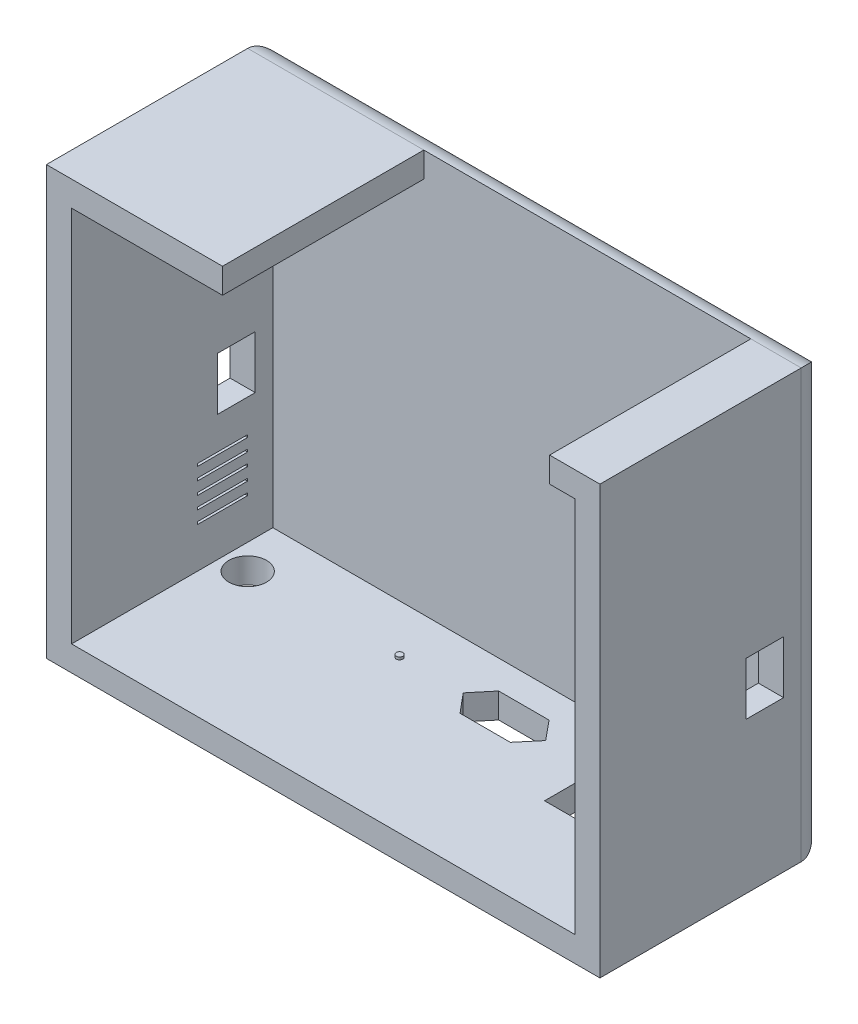
SolidWorks part; units mm, degrees
ref_plane "Front Plane" through (0, 0, 0) normal (0, 0, 1) x (1, 0, 0)
ref_plane "Top Plane" through (0, 0, 0) normal (0, 1, 0) x (1, 0, 0)
ref_plane "Right Plane" through (0, 0, 0) normal (1, 0, 0) x (0, 0, -1)
sketch "Sketch1" plane through (0, 0, 0) normal (0, 0, 1) x (1, 0, 0)
  line L1 (-465.1793, 299.9736) -> (-245.1793, 299.9736)
  line L2 (-465.1793, 299.9736) -> (-465.1793, 129.9736)
  line L3 (-465.1793, 129.9736) -> (-245.1793, 129.9736)
  line L4 (-245.1793, 299.9736) -> (-245.1793, 129.9736)
  dimension "D1" = 170
  dimension "D2" = 220
extrude "Boss-Extrude1" add sketch "Sketch1" along normal blind 100
sketch "Sketch3" plane through (0, 0, 100) normal (0, 0, 1) x (1, 0, 0)
  line L1 (-455.1793, 289.9736) -> (-255.1793, 289.9736)
  line L2 (-455.1793, 289.9736) -> (-455.1793, 139.9736)
  line L3 (-455.1793, 139.9736) -> (-255.1793, 139.9736)
  line L4 (-255.1793, 289.9736) -> (-255.1793, 139.9736)
  dimension "D1" = 10
  dimension "D2" = 10
  dimension "D3" = 10
  dimension "D4" = 10
  dimension "D5" = 10
  dimension "D6" = 150
  dimension "D7" = 200
extrude "Cut-Extrude2" cut sketch "Sketch3" against normal blind 90
fillet "Fillet1" radius 10 4 edges at (-355.1793, 129.9736, 0) (-245.1793, 214.9736, 0) (-355.1793, 299.9736, 0) (-465.1793, 214.9736, 0)
sketch "Sketch4" plane through (0, 299.9736, 0) normal (0, 1, 0) x (1, 0, 0)
  line L0 (-245.1793, -10) -> (-465.1793, -10) construction
  line L1 (-265.1793, -100) -> (-395.1793, -100)
  line L2 (-265.1793, -100) -> (-265.1793, -10)
  line L3 (-265.1793, -10) -> (-395.1793, -10)
  line L4 (-395.1793, -100) -> (-395.1793, -10)
  line L5 (-255.1793, -10) -> (-255.1793, -100) construction
  line L7 (-245.1793, -100) -> (-465.1793, -100) construction
  dimension "D1" = 10
  dimension "D2" = 0
  dimension "D3" = 130
  dimension "D4" = 90
extrude "Cut-Extrude3" cut sketch "Sketch4" against normal blind 10
ref_plane "Plane1" through (0, 0, 90) normal (0, 0, 1) x (1, 0, 0)
sketch "Sketch8" plane through (0, 0, 90) normal (0, 0, 1) x (1, 0, 0)
  line L1 (-466.5662, 301.0824) -> (-243.038, 301.0824)
  line L2 (-466.5662, 301.0824) -> (-466.5662, 129.2049)
  line L3 (-466.5662, 129.2049) -> (-243.038, 129.2049)
  line L4 (-243.038, 301.0824) -> (-243.038, 129.2049)
extrude "Cut-Extrude5" cut sketch "Sketch8" along normal blind 10
sketch "Sketch9" plane through (0, 129.9736, 0) normal (0, -1, 0) x (1, 0, 0)
  circle A0 centre (-445.1793, 30) radius 7.5
  dimension "D1" = 20
  dimension "D3" = 15
  dimension "D2" = 20
extrude "Cut-Extrude7" cut sketch "Sketch9" against normal up to next
sketch "Sketch10" plane through (0, 129.9736, 0) normal (0, -1, 0) x (1, 0, 0)
  line L1 (-307.1793, 50) -> (-257.1793, 50)
  line L2 (-307.1793, 50) -> (-307.1793, 20)
  line L3 (-307.1793, 20) -> (-257.1793, 20)
  line L4 (-257.1793, 50) -> (-257.1793, 20)
  dimension "D1" = 30
  dimension "D2" = 50
  dimension "D3" = 12
  dimension "D4" = 10
extrude "Cut-Extrude8" cut sketch "Sketch10" against normal up to next
sketch "Sketch11" plane through (-465.1793, 0, 0) normal (-1, 0, 0) x (0, 0, 1)
  line L0 (40.0406, 162.0359) -> (40.0406, 161.0359)
  line L1 (40.0406, 157.0359) -> (20.0406, 157.0359)
  line L2 (40.0406, 157.0359) -> (40.0406, 156.0359)
  line L3 (40.0406, 156.0359) -> (20.0406, 156.0359)
  line L4 (20.0406, 157.0359) -> (20.0406, 156.0359)
  line L5 (40.0406, 162.0359) -> (20.0406, 162.0359)
  line L6 (20.0406, 162.0359) -> (20.0406, 161.0359)
  line L7 (40.0406, 161.0359) -> (20.0406, 161.0359)
  line L8 (40.0406, 167.0359) -> (40.0406, 166.0359)
  line L9 (40.0406, 167.0359) -> (20.0406, 167.0359)
  line L10 (20.0406, 167.0359) -> (20.0406, 166.0359)
  line L11 (40.0406, 166.0359) -> (20.0406, 166.0359)
  line L12 (40.0406, 172.0359) -> (40.0406, 171.0359)
  line L13 (40.0406, 172.0359) -> (20.0406, 172.0359)
  line L14 (20.0406, 172.0359) -> (20.0406, 171.0359)
  line L15 (40.0406, 171.0359) -> (20.0406, 171.0359)
  line L16 (40.0406, 177.0359) -> (40.0406, 176.0359)
  line L17 (40.0406, 177.0359) -> (20.0406, 177.0359)
  line L18 (20.0406, 177.0359) -> (20.0406, 176.0359)
  line L19 (40.0406, 176.0359) -> (20.0406, 176.0359)
  dimension "D1" = 20
  dimension "D2" = 1
  dimension "D3" = 5
extrude "Cut-Extrude9" cut sketch "Sketch11" against normal up to next
sketch "Sketch12" plane through (0, 129.9736, 0) normal (0, -1, 0) x (1, 0, 0)
  line L0 (-354.0977, 36.6831) -> (-334.0977, 36.6831)
  line L2 (-334.0977, 36.6831) -> (-327.6977, 29.0559)
  line L3 (-327.6977, 29.0559) -> (-335.3582, 22.628)
  line L4 (-335.3582, 22.628) -> (-352.7907, 22.628)
  line L5 (-352.7907, 22.628) -> (-360.4977, 29.0233)
  line L6 (-360.4977, 29.0233) -> (-354.0977, 36.6831)
  dimension "D1" = 20
  dimension "D2" = 50.12
  dimension "D3" = 50
  dimension "D6" = 6.4
  dimension "D7" = 6.4
extrude "Cut-Extrude10" cut sketch "Sketch12" against normal up to next contours L6 L0 L2 L3 L4 L5
sketch "Sketch13" plane through (0, 129.9736, 0) normal (0, -1, 0) x (1, 0, 0)
  line L0 (-327.6977, 29.0559) -> (-334.0458, 21.3292)
  line L2 (-327.6977, 29.0559) -> (-335.3582, 22.628)
  line L3 (-334.0458, 21.3292) -> (-334.0458, 23.7292)
  line L6 (-354.1102, 21.3292) -> (-360.4977, 29.0233)
  line L7 (-354.1102, 21.3292) -> (-354.1177, 23.7292)
  line L8 (-352.7907, 22.628) -> (-360.4977, 29.0233) construction
  line L9 (-360.4977, 29.0233) -> (-354.1177, 23.7292)
  line L10 (-354.1102, 21.3292) -> (-334.0458, 21.3292)
  line L11 (-334.0458, 22.628) -> (-354.114, 22.5292)
  line L12 (-354.114, 22.5292) -> (-354.1102, 21.3292)
  line M10 (-352.7907, 22.628) -> (-360.4977, 29.0233)
  line M14 (-327.6977, 29.0559) -> (-335.3582, 22.628)
  dimension "D1" = 10
  dimension "D2" = 2.4
  dimension "D3" = 10
  dimension "D4" = 2.4
extrude "Cut-Extrude11" cut sketch "Sketch13" against normal blind 10 contours L6 L7 M10 | L3 L0 M14 region at (-331.9298, 129.9736, 24.7047) region at (-356.2419, 129.9736, 24.6939)
sketch "Sketch14" plane through (0, 129.9736, 0) normal (0, -1, 0) x (1, 0, 0)
  line L0 (-354.1177, 23.7292) -> (-354.1102, 21.3292)
  line L1 (-354.1102, 21.3292) -> (-334.0458, 21.3292)
  line L2 (-334.0458, 21.3292) -> (-334.0458, 23.7292)
  line L3 (-334.0458, 23.7292) -> (-354.1177, 23.7292)
extrude "Cut-Extrude12" cut sketch "Sketch14" against normal up to next
sketch "Sketch15" plane through (0, 129.9736, 0) normal (0, -1, 0) x (1, 0, 0)
  circle A0 centre (-385.4087, 29.4141) radius 5.8633
extrude "Cut-Extrude13" cut sketch "Sketch15" against normal blind 8
sketch "Sketch16" plane through (0, 137.9736, 0) normal (0, -1, 0) x (1, 0, 0)
  circle A0 centre (-385.4087, 29.4141) radius 1.3
  point P0 (-385.4087, 29.4141)
extrude "Boss-Extrude3" add sketch "Sketch16" along normal blind 8 and the other way blind 3
sketch "Sketch17" plane through (0, 129.9736, 0) normal (0, -1, 0) x (1, 0, 0)
  circle A0 centre (-385.4087, 29.4141) radius 9.826
extrude "Extrude-Thin1" add sketch "Sketch17" along normal blind 8 thin thin type mid plane wall 8
fillet "Fillet2" radius 8 1 edges at (-371.5828, 121.9736, 29.4141)
sketch "Sketch18" plane through (-245.1793, 0, 0) normal (1, 0, 0) x (0, 0, -1)
  line L1 (-10, 129.9736) -> (-10, 299.9736) construction
  line L10 (-32, 189.9736) -> (-17, 189.9736)
  line L11 (-32, 189.9736) -> (-32, 210.9736)
  line L12 (-32, 210.9736) -> (-17, 210.9736)
  line L13 (-17, 189.9736) -> (-17, 210.9736)
  point P2 (-10, 169.9736)
  dimension "D1" = 40
  dimension "D2" = 20
  dimension "D3" = 7
  dimension "D4" = 15
  dimension "D5" = 21
extrude "Cut-Extrude14" cut sketch "Sketch18" against normal blind 249
